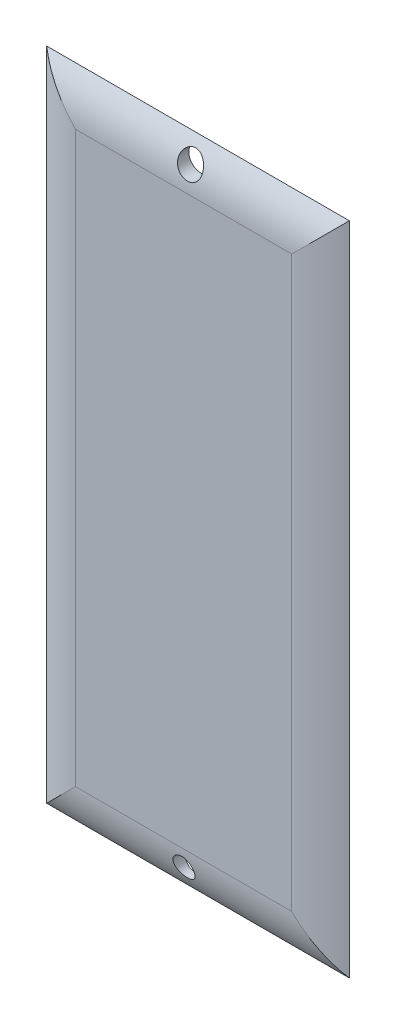
SolidWorks part; units mm, degrees
ref_plane "Front Plane" through (0, 0, 0) normal (0, 0, 1) x (1, 0, 0)
ref_plane "Top Plane" through (0, 0, 0) normal (0, 1, 0) x (1, 0, 0)
ref_plane "Right Plane" through (0, 0, 0) normal (1, 0, 0) x (0, 0, -1)
sketch "Sketch1" plane through (0, 0, 0) normal (0, 0, 1) x (1, 0, 0)
  line L0 (-21, 45.5) -> (21, 45.5)
  line L1 (-21, 45.5) -> (-21, -45.5)
  line L2 (-21, -45.5) -> (21, -45.5)
  line L3 (21, 45.5) -> (21, -45.5)
extrude "Boss-Extrude1" add sketch "Sketch1" along normal blind 2
sketch "Sketch2" plane through (0, 0, 2) normal (0, 0, 1) x (1, 0, 0)
  circle A0 centre (-0.2831, -42.0494) radius 1.4923
  circle A1 centre (0.4384, 42.637) radius 1.7139
extrude "Cut-Extrude1" cut sketch "Sketch2" against normal blind 2
fillet "Fillet1" radius 10 4 edges at (0, 45.5, 2) (-21, 0, 2) (21, 0, 2) (0, -45.5, 2)
